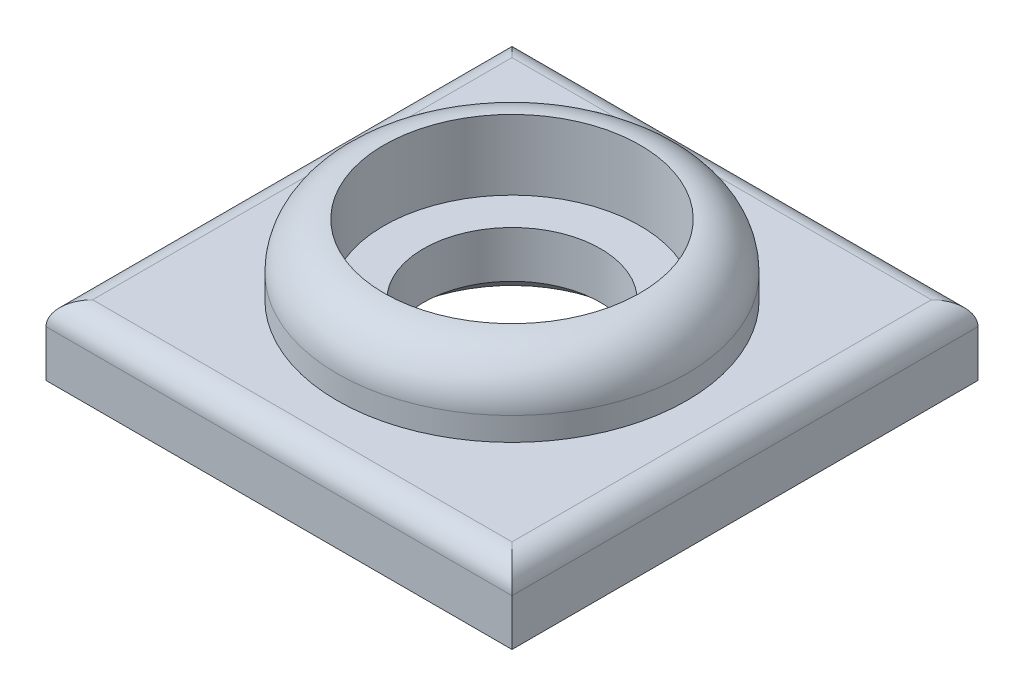
SolidWorks part; units mm, degrees
ref_plane "Спереди" through (0, 0, 0) normal (0, 0, 1) x (1, 0, 0)
ref_plane "Сверху" through (0, 0, 0) normal (0, 1, 0) x (1, 0, 0)
ref_plane "Справа" through (0, 0, 0) normal (1, 0, 0) x (0, 0, -1)
sketch "Sketch1" plane through (0, 0, 0) normal (0, 1, 0) x (1, 0, 0)
  line L1 (10, -10) -> (-10, -10)
  line L2 (10, -10) -> (10, 10)
  line L3 (10, 10) -> (-10, 10)
  line L4 (-10, -10) -> (-10, 10)
  line L5 (10, -10) -> (-10, 10) construction
  line L6 (10, 10) -> (-10, -10) construction
  circle A0 centre (0, 0) radius 3.8
  point P0 (0, 0)
  dimension "D2" = 7.6
  dimension "D1" = 20
extrude "Boss-Extrude1" add sketch "Sketch1" along normal blind 3
fillet "Fillet1" radius 1 4 edges at (0, 3, -10) (10, 3, 0) (0, 3, 10) (-10, 3, 0)
chamfer "Chamfer1" distance 1 angle 50 1 edges at (0, 0, 3.8) first distance on face at (0, 3, 3.8)
sketch "Sketch2" plane through (0, 3, 0) normal (0, 1, 0) x (1, 0, 0)
  circle A0 centre (0, 0) radius 5.5
  circle A1 centre (0, 0) radius 7.5
  dimension "D1" = 2
  dimension "D2" = 11
extrude "Boss-Extrude2" add sketch "Sketch2" along normal blind 3
fillet "Fillet2" radius 2 1 edges at (0, 6, 7.5)
